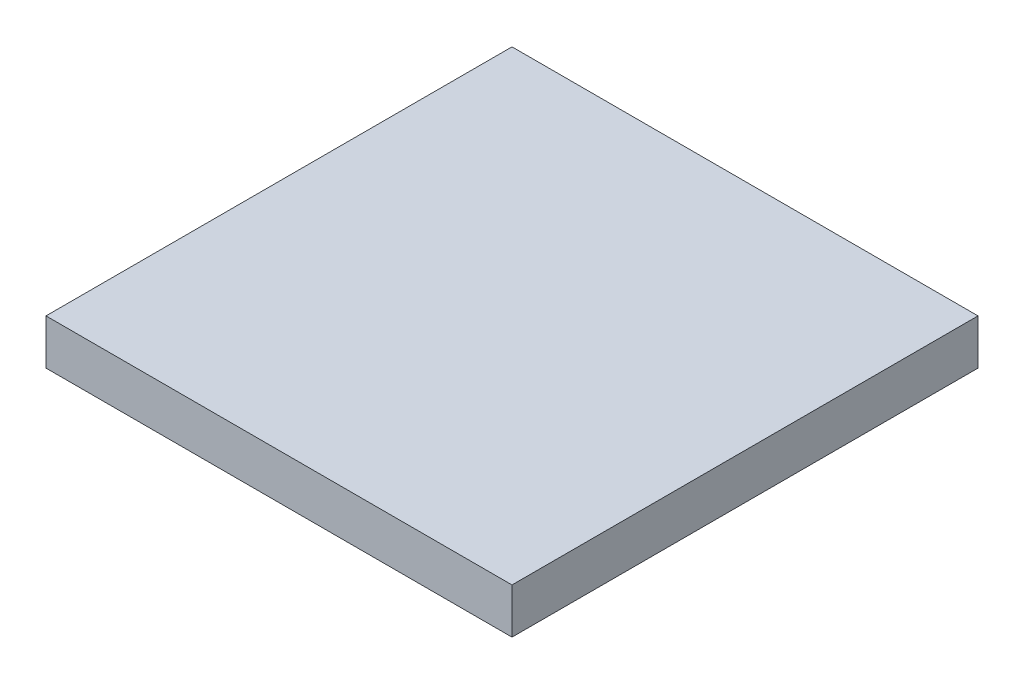
SolidWorks part; units mm, degrees
ref_plane "Front Plane" through (0, 0, 0) normal (0, 0, 1) x (1, 0, 0)
ref_plane "Top Plane" through (0, 0, 0) normal (0, 1, 0) x (1, 0, 0)
ref_plane "Right Plane" through (0, 0, 0) normal (1, 0, 0) x (0, 0, -1)
sketch "Sketch1" plane through (0, 0, 0) normal (0, 1, 0) x (1, 0, 0)
  line L1 (-5.15, -5.15) -> (5.15, -5.15)
  line L2 (-5.15, -5.15) -> (-5.15, 5.15)
  line L3 (-5.15, 5.15) -> (5.15, 5.15)
  line L4 (5.15, -5.15) -> (5.15, 5.15)
  line L5 (-5.15, -5.15) -> (5.15, 5.15) construction
  line L6 (-5.15, 5.15) -> (5.15, -5.15) construction
  point P0 (0, 0)
  dimension "D1" = 10.3
  dimension "D2" = 10.3
extrude "chip_lid" add sketch "Sketch1" along normal blind 1
equation "\"pcb_length\"= 26.0 ' length of the chip in the direction of the feadline"
equation "\"pcb_side\"= 10    ' length of the chip in the other direction"
equation "\"pcb_width\"= 0.381 ' thickness of the PCB (381 um)"
equation "\"wall_width\"= 1  ' minimal width from the box walls"
equation "\"route_width\"= 0.5 ' The width of the trace on the lid for not touching the signal roates."
equation "\"route_clearence\"= 0.04 ' The clearence depth of the trace on the lid for not touching the signal roates."
equation "\"route_chip_clearence\"= 0"
equation "\"port_count\"= 2"
equation "\"port_space\"= 1.5"
equation "\"port_length\"= 5.1"
equation "\"port_width\"= 5.1"
equation "\"chip_length\"= 6.3 ' length of the chip in the direction of the feadline"
equation "\"chip_side\"= 6.3 ' length of the chip in the other direction"
equation "\"pedestal_depth\"= 0.0 ' depth of the pedestal under the chip"
equation "\"chip_leg\"= 0.8  ' size of the legs the chip lay on in case there is pedestal"
equation "\"wing_length\"= 5 ' Mounting wing size"
equation "\"wing_width\"= 1 ' mounting wing width"
equation "\"bonding_clearence\"= 1"
equation "\"box_height\"= \"wall_width\" + \"pedestal_depth\" + \"pcb_width\""
equation "\"box_length\"= \"pcb_length\" + 2 * \"wall_width\""
equation "\"box_side\"= \"pcb_side\" + 2 * \"wall_width\""
equation "\"D1@Sketch1\"=\"chip_length\"+2*\"wall_width\"+2*\"bonding_clearence\""
equation "\"D1@chip_lid\" = \"wall_width\""
equation "\"D2@Sketch1\"=\"chip_side\"+2*\"wall_width\"+2*\"bonding_clearence\""
equation "\"chip_width\"= 0.381 ' thickness of the chip (381 um)"
